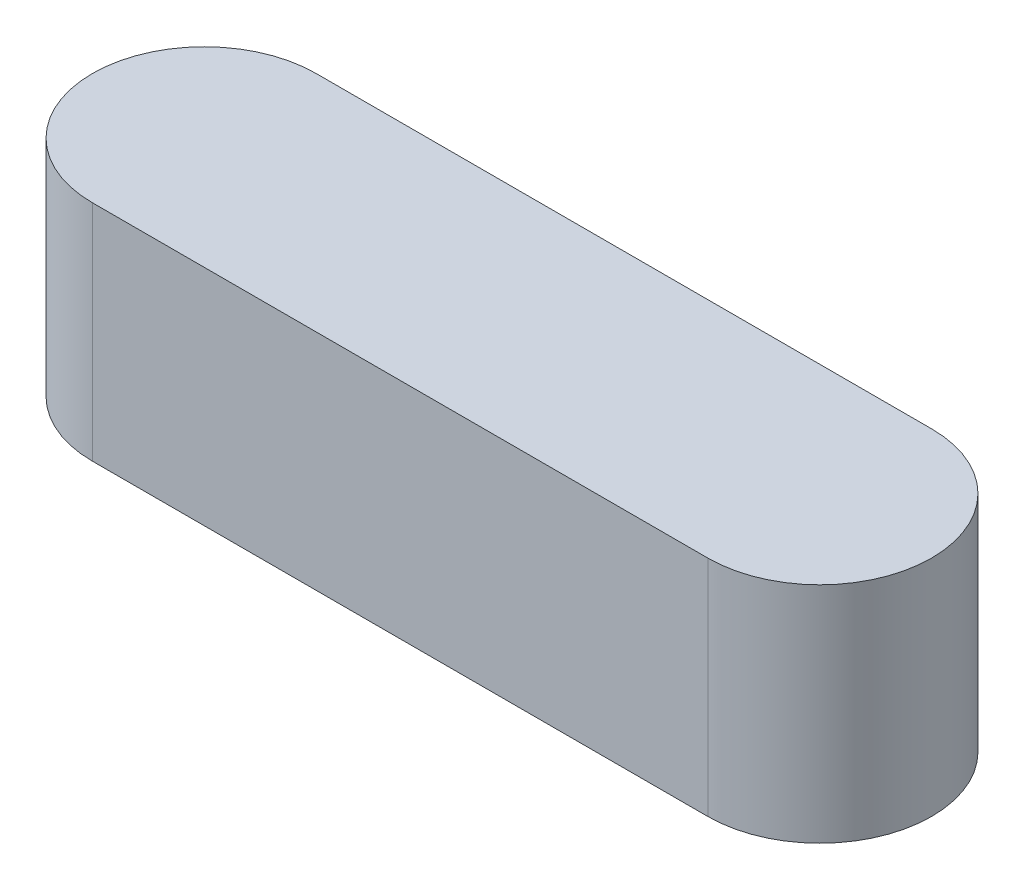
SolidWorks part; units mm, degrees
ref_plane "Front Plane" through (0, 0, 0) normal (0, 0, 1) x (1, 0, 0)
ref_plane "Top Plane" through (0, 0, 0) normal (0, 1, 0) x (1, 0, 0)
ref_plane "Right Plane" through (0, 0, 0) normal (1, 0, 0) x (0, 0, -1)
sketch "Sketch1" plane through (0, 0, 0) normal (0, 1, 0) x (1, 0, 0)
  line L0 (-27.5, 0) -> (27.5, 0) construction
  line L1 (-27.5, 10) -> (27.5, 10)
  line L2 (-27.5, -10) -> (27.5, -10)
  arc A0 (-27.5, 10) -> (-27.5, -10) centre (-27.5, 0) ccw
  arc A1 (27.5, -10) -> (27.5, 10) centre (27.5, 0) ccw
  point P3 (0, 0)
  dimension "D1" = 10
  dimension "D2" = 55
extrude "Boss-Extrude1" add sketch "Sketch1" along normal blind 20
equation "\"Length\"= 55mm"
equation "\"Radius\"= 10mm"
equation "\"Thickness\"= 20mm"
equation "\"D1@Sketch1\"= \"Radius\""
equation "\"D2@Sketch1\" = \"Length\""
equation "\"D1@Boss-Extrude1\"= \"Thickness\""
